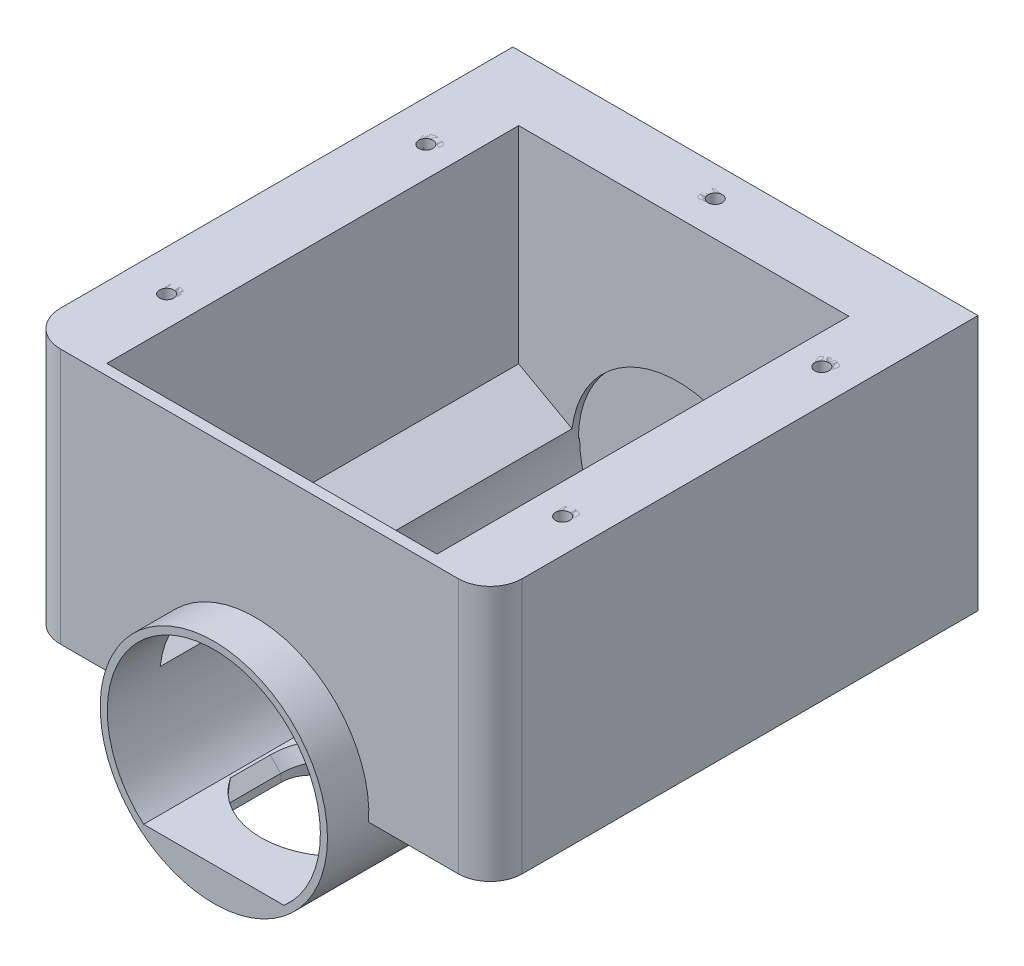
SolidWorks part; units mm, degrees
ref_plane "Front Plane" through (0, 0, 0) normal (0, 0, 1) x (1, 0, 0)
ref_plane "Top Plane" through (0, 0, 0) normal (0, 1, 0) x (1, 0, 0)
ref_plane "Right Plane" through (0, 0, 0) normal (1, 0, 0) x (0, 0, -1)
sketch "Sketch1" plane through (0, 0, 0) normal (0, 0, 1) x (1, 0, 0)
  circle A0 centre (0, 0) radius 30
  circle A1 centre (0, 0) radius 32
  dimension "D1" = 60
  dimension "D2" = 2
extrude "Boss-Extrude1" add sketch "Sketch1" along normal blind 60
sketch "Sketch3" plane through (0, 0, 0) normal (0, 0, -1) x (-1, 0, 0)
  line L0 (-32, 0) -> (-30, 0)
  line L2 (30, 0) -> (32, 0)
  arc A0 (-30, 0) -> (30, 0) centre (0, 0) ccw
  arc A1 (-32, 0) -> (32, 0) centre (0, 0) ccw
extrude "Boss-Extrude3" add sketch "Sketch3" along normal blind 120 contours A1 L2 A0 L0
sketch "Sketch4" plane through (0, 0, -120) normal (0, 0, -1) x (-1, 0, 0)
  circle A0 centre (0, 0) radius 32
extrude "Boss-Extrude4" add sketch "Sketch4" along normal blind 3 contours A0
sketch "Sketch5" plane through (0, 0, -123) normal (0, 0, -1) x (-1, 0, 0)
  line L5 (-1.05, 9.55) -> (1.05, 9.55)
  line L6 (-1.05, 9.55) -> (-1.05, 8.4349)
  line L12 (1.05, 9.55) -> (1.05, 8.4349)
  line L16 (-1.05, -8.4349) -> (-1.05, -9.55)
  line L17 (-1.05, -9.55) -> (1.05, -9.55)
  line L18 (1.05, -8.4349) -> (1.05, -9.55)
  arc A1 (1.05, -8.4349) -> (1.05, 8.4349) centre (0, 0) ccw
  arc A2 (-1.05, 8.4349) -> (-1.05, -8.4349) centre (0, 0) ccw
  point P3 (0, 8.5)
  point P8 (0, -8.5)
  dimension "D1" = 17
  dimension "D2" = 2.1
extrude "Cut-Extrude2" cut sketch "Sketch5" against normal blind 3
ref_plane "Plane1" through (0, 0, 0) normal (0, 1, 0) x (1, 0, 0)
sketch "Sketch6" plane through (0, 0, 0) normal (0, 1, 0) x (1, 0, 0)
  line L0 (32, 120) -> (30, 120) construction
  line L1 (-32, 0) -> (31.9951, 0)
  line L2 (-32, 0) -> (-32, 120)
  line L3 (-32, 120) -> (31.9951, 120)
  line L4 (31.9951, 0) -> (31.9951, 120)
  line L6 (-46.8095, 119.6619) -> (53.1905, 119.6619)
  line L7 (-46.8095, 119.6619) -> (-46.8095, -0.3381)
  line L8 (-46.8095, -0.3381) -> (53.1905, -0.3381)
  line L9 (53.1905, 119.6619) -> (53.1905, -0.3381)
  line L10 (-44.8095, 117.6619) -> (51.1905, 117.6619)
  line L11 (-44.8095, 117.6619) -> (-44.8095, 1.6619)
  line L12 (-44.8095, 1.6619) -> (51.1905, 1.6619)
  line L13 (51.1905, 117.6619) -> (51.1905, 1.6619)
  dimension "D1" = 100
  dimension "D2" = 2
  dimension "D3" = 2
  dimension "D4" = 2
  dimension "D5" = 2
extrude "Boss-Extrude11" add sketch "Sketch6" against normal blind 2 contours L10 L13 L12 L4 L1 L2 L11 L6 L7 L8 L9 | L2 L10 L4 L6 | L12 L2 L1 L4 region at (-0.0025, 0, -0.831) region at (-0.0025, 0, 0.1562) region at (-0.0025, 0, -118.6619)
extrude "Boss-Extrude12" add sketch "Sketch6<8>" along normal blind 70 contours L2 L10 L4 L6 | L10 L13 L12 L4 L1 L2 L11 L6 L7 L8 L9 | L12 L2 L1 L4 region at (-0.0025, 0, -0.831) region at (-0.0025, 0, 0.1562) region at (-0.0025, 0, -118.6619)
sketch "Sketch6<8>" plane through (0, 0, 0) normal (0, 1, 0) x (1, 0, 0) same geometry as "Sketch6"
ref_plane "Plane2" through (0, 0, -117.6619) normal (0, 0, 1) x (1, 0, 0)
sketch "Sketch8" plane through (0, 0, -119.6619) normal (0, 0, -1) x (-1, 0, 0)
  line L0 (46.8095, 13) -> (19.6795, -2)
  line L1 (-53.1905, -2) -> (-26.0645, -2)
  line L2 (-53.1905, -2) -> (-53.1905, 14)
  line L5 (46.8095, -2) -> (19.6795, -2)
  line L6 (46.8095, -2) -> (46.8095, 13)
  line L9 (-53.1905, 14) -> (-26.0645, -2)
  dimension "D1" = 16
  dimension "D2" = 27.13
  dimension "D4" = 15
extrude "Boss-Extrude14" add sketch "Sketch8" against normal blind 120
ref_plane "Plane3" through (0, 0, 60) normal (0, 0, 1) x (1, 0, 0)
sketch "Sketch10" plane through (0, 0, 60) normal (0, 0, 1) x (1, 0, 0)
  circle A0 centre (0, 0) radius 30
extrude "Cut-Extrude3" cut sketch "Sketch10" against normal blind 180 contours A0
ref_plane "Plane4" through (0, -2, 0) normal (0, -1, 0) x (-1, 0, 0)
sketch "Sketch11" plane through (0, -2, 0) normal (0, -1, 0) x (-1, 0, 0)
  line L0 (0, 123) -> (0, -60) construction
  line L1 (32, 123) -> (-32, 123) construction
  line L2 (-32, -60) -> (32, -60) construction
  circle A0 centre (0, 106.678) radius 2
  circle A1 centre (0, 74.9444) radius 2
  circle A2 centre (0, 18.4657) radius 2
  circle A3 centre (0, 43.5664) radius 2
  dimension "D1" = 31.7336
ref_plane "Plane5" through (0, 0, 60) normal (0, 0, 1) x (1, 0, 0)
sketch "Sketch12" plane through (0, 0, 60) normal (0, 0, 1) x (1, 0, 0)
  line L0 (0, -40) -> (0, 0.6822) construction
  circle A5 centre (0, 0) radius 32
  circle A6 centre (0, -26.2661) radius 13.6282
  circle A7 centre (0, -26.2661) radius 11.6282
  point P9 (0, -26.2661)
  dimension "D1" = 2
  dimension "D2" = 64
extrude "Boss-Extrude16" add sketch "Sketch12<4>" against normal blind 71 contours A7 L0 A5 | L0 A7 A5 region at (-4.4798, -34.0319, 60) region at (4.4798, -34.0319, 60)
sketch "Sketch12<4>" plane through (0, 0, 60) normal (0, 0, 1) x (1, 0, 0) same geometry as "Sketch12"
extrude "Cut-Extrude6" cut sketch "Sketch12<5>" against normal blind 69 contours L0 A7 A5 | A7 L0 A5 | L0 A6 A5 A7 | A6 L0 A7 A5 region at (-7.1656, -35.6219, 60) region at (7.1656, -35.6219, 60) region at (-4.4798, -34.0319, 60) region at (4.4798, -34.0319, 60)
sketch "Sketch12<5>" plane through (0, 0, 60) normal (0, 0, 1) x (1, 0, 0) same geometry as "Sketch12"
sketch "Sketch13" plane through (0, 0, -119.6619) normal (0, 0, -1) x (-1, 0, 0)
  line L0 (31.9374, -2) -> (46.8095, -2)
  line L1 (-53.1905, 70) -> (46.8095, 70)
  line L2 (-53.1905, 70) -> (-53.1905, -2)
  line L3 (-53.1905, -2) -> (-31.9374, -2)
  line L4 (46.8095, 70) -> (46.8095, -2)
  arc A0 (31.9374, -2) -> (-31.9374, -2) centre (0, 0) ccw
extrude "Boss-Extrude17" add sketch "Sketch13" along normal blind 3.35
ref_plane "Plane6" through (0, -45, 0) normal (0, -1, 0) x (-1, 0, 0)
ref_plane "Plane7" through (0, 0, -9) normal (0, 0, 1) x (1, 0, 0)
extrude "Cut-Extrude11" cut sketch "Sketch12" against normal blind 110 contours A7 L0 A5 | L0 A7 A5 | A6 L0 A7 A5 | L0 A6 A5 A7 region at (-7.1656, -35.6219, 60) region at (7.1656, -35.6219, 60) region at (-4.4798, -34.0319, 60) region at (4.4798, -34.0319, 60)
ref_plane "Plane8" through (-46.8095, 0, 0) normal (-1, 0, 0) x (0, 0, 1)
sketch "Sketch16" plane through (-46.8095, 0, 0) normal (-1, 0, 0) x (0, 0, 1)
  line L3 (23, -32) -> (60, -32)
  line L4 (60, 32) -> (60, -32)
  line L5 (60, 32) -> (23, 32)
  line L6 (60, 32) -> (0.3381, 32) construction
  line L7 (23, 32) -> (23, -32)
  dimension "D1" = 37
ref_plane "Plane10" through (0, -52, 0) normal (0, -1, 0) x (-1, 0, 0)
sketch "Sketch18" plane through (0, -52, 0) normal (0, -1, 0) x (-1, 0, 0)
  line L0 (0, 0) -> (0, 21.7329) construction
  line L1 (-15.8772, 6.8416) -> (-15.8772, 21.7329)
  line L2 (15.8772, 6.8416) -> (15.8772, 21.7329)
  arc A1 (15.8772, 21.7329) -> (-15.8772, 21.7329) centre (0, 21.7329) ccw
  arc A2 (15.8772, 6.8416) -> (-15.8772, 6.8416) centre (0, 22.7187) cw
  point P3 (0, 10.8665)
extrude "Cut-Extrude15" cut sketch "Sketch16" against normal blind 94
extrude "Cut-Extrude16" cut sketch "Sketch18" against normal blind 34
sketch "Sketch19" plane through (0, 70, 0) normal (0, 1, 0) x (1, 0, 0)
  line L0 (-46.8095, 123.0119) -> (53.1905, 123.0119) construction
  line L1 (-56.8095, 133.0119) -> (63.1905, 133.0119)
  line L2 (-56.8095, 133.0119) -> (-56.8095, 2.6619)
  line L3 (-56.8095, -0.3381) -> (-46.8095, -0.3381)
  line L4 (63.1905, 133.0119) -> (63.1905, 2.6619)
  line L5 (53.1905, 123.0119) -> (53.1905, -0.3381) construction
  line L6 (-46.8095, 123.0119) -> (-46.8095, -0.3381) construction
  line L7 (-46.8095, -0.3381) -> (53.1905, -0.3381) construction
  line L8 (-56.8095, 2.6619) -> (-46.8095, 2.6619)
  line L9 (-59.8095, 136.0119) -> (66.1905, 136.0119)
  line L10 (-59.8095, 136.0119) -> (-59.8095, -0.3381)
  line L11 (-59.8095, -0.3381) -> (-46.8095, -0.3381)
  line L12 (66.1905, 136.0119) -> (66.1905, -0.3381)
  line L13 (53.1905, -0.3381) -> (53.1905, 2.6619)
  line L14 (-46.8095, -0.3381) -> (-46.8095, 2.6619)
  line L15 (53.1905, 2.6619) -> (63.1905, 2.6619)
  line L16 (53.1905, -0.3381) -> (63.1905, -0.3381)
  line L17 (53.1905, -0.3381) -> (66.1905, -0.3381)
  line L19 (63.1905, 2.6619) -> (-56.8095, 2.6619)
  line L20 (63.1905, 2.6619) -> (63.1905, 133.0119)
  line L21 (63.1905, 133.0119) -> (-56.8095, 133.0119)
  line L22 (-56.8095, 2.6619) -> (-56.8095, 133.0119)
  line M12 (53.1905, -0.3381) -> (53.1905, 123.0119)
  line M13 (53.1905, 123.0119) -> (-46.8095, 123.0119)
  line M14 (-46.8095, 123.0119) -> (-46.8095, -0.3381)
  dimension "D1" = 10
  dimension "D2" = 10
  dimension "D3" = 10
  dimension "D4" = 3
  dimension "D5" = 3
  dimension "D6" = 3
  dimension "D7" = 3
extrude "Boss-Extrude20" add sketch "Sketch19" against normal blind 72 contours L16 L17 L12 L9 L10 L11 L3 L8 L2 L1 L4 L15 M14 M12 region at (-58.6661, 70, -67.8369)
extrude "Boss-Extrude21" add sketch "Sketch19<4>" against normal blind 3 contours L15 L4 L1 L2 L8 M12 M14 M13 region at (3.1905, 70, -131.2402)
sketch "Sketch19<4>" plane through (0, 70, 0) normal (0, 1, 0) x (1, 0, 0) same geometry as "Sketch19"
sketch "Sketch21" plane through (0, 0, -123) normal (0, 0, -1) x (-1, 0, 0)
  circle A0 centre (0, 0) radius 32
extrude "Cut-Extrude17" cut sketch "Sketch21" along normal blind 34
sketch "Sketch22" plane through (0, 0, -136.0119) normal (0, 0, -1) x (-1, 0, 0)
  line L0 (59.8095, 70) -> (-66.1905, 70) construction
  line L1 (-66.1905, 70) -> (-51.1905, 70)
  line L2 (-66.1905, 70) -> (-66.1905, 57)
  line L3 (-66.1905, 57) -> (-51.1905, 57)
  line L4 (-51.1905, 70) -> (-51.1905, 57)
  line L6 (44.3736, 70) -> (59.8095, 70)
  line L7 (44.3736, 70) -> (44.3736, 57)
  line L8 (44.3736, 57) -> (59.8095, 57)
  line L9 (59.8095, 70) -> (59.8095, 57)
  line L10 (59.8095, -2) -> (59.8095, 70) construction
  circle A0 centre (-58.6905, 63.5) radius 1.5
  circle A1 centre (52.0916, 63.5) radius 1.5
  dimension "D4" = 3
  dimension "D1" = 13
  dimension "D2" = 15
  dimension "D3" = 13
extrude "Boss-Extrude23" add sketch "Sketch22" against normal blind 10
extrude "Cut-Extrude19" cut sketch "Sketch22<2>" against normal blind 17 and the other way blind 20 contours A0 | A1
sketch "Sketch22<2>" plane through (0, 0, -136.0119) normal (0, 0, -1) x (-1, 0, 0) same geometry as "Sketch22"
sketch "Sketch23" plane through (0, 0, 23) normal (0, 0, 1) x (1, 0, 0)
  line L2 (-19.7809, -22.5547) -> (19.7809, -22.5547)
  arc A0 (-19.7809, -22.5547) -> (19.7809, -22.5547) centre (0, 0) ccw
extrude "Boss-Extrude24" add sketch "Sketch23" against normal blind 145
ref_plane "Plane11" through (19.7809, -22.5547, 23) normal (0, 0, 1) x (1, 0, 0)
ref_plane "Plane12" through (0, 0, -37.6101) normal (0, 0, 1) x (1, 0, 0)
sketch "Sketch25" plane through (0, 0, -37.6101) normal (0, 0, 1) x (1, 0, 0)
  circle A0 centre (19.7809, -22.5547) radius 1.2
  circle A1 centre (-19.7809, -22.5547) radius 1.2
extrude "Cut-Extrude21" cut sketch "Sketch25" against normal blind 82
ref_plane "Plane15" through (0, -22.5547, 0) normal (0, 1, 0) x (1, 0, 0)
extrude "Cut-Extrude22" cut sketch "Sketch18<3>" against normal blind 36
sketch "Sketch18<3>" plane through (0, -52, 0) normal (0, -1, 0) x (-1, 0, 0) same geometry as "Sketch18"
ref_plane "Plane17" through (0, 0, 0.3381) normal (0, 0, 1) x (1, 0, 0)
sketch "Sketch29" plane through (0, 0, 0.3381) normal (0, 0, 1) x (1, 0, 0)
  line L0 (-59.8095, -2) -> (-31.9374, -2) construction
  line L1 (31.9374, -2) -> (66.1905, -2) construction
  line L2 (66.1905, -2) -> (66.1905, 70) construction
  line L3 (-59.8095, 70) -> (66.1905, 70) construction
  line L4 (-59.8095, -2) -> (-59.8095, 70) construction
  line L5 (-59.8095, -2) -> (-31.9374, -2)
  line L6 (31.9374, -2) -> (66.1905, -2)
  line L7 (66.1905, -2) -> (66.1905, 70)
  line L8 (-59.8095, 70) -> (66.1905, 70)
  line L9 (-59.8095, -2) -> (-59.8095, 70)
  arc A0 (31.9374, -2) -> (-31.9374, -2) centre (0, 0) ccw construction
  arc A1 (31.9374, -2) -> (-31.9374, -2) centre (0, 0) ccw
extrude "Boss-Extrude34" add sketch "Sketch29" along normal blind 1
sketch "Sketch30" plane through (-59.8095, 0, 0) normal (-1, 0, 0) x (0, 0, 1)
  line L1 (-136.0119, 70) -> (1.3381, 70)
  line L2 (-136.0119, 70) -> (-136.0119, -2)
  line L3 (-136.0119, -2) -> (1.3381, -2)
  line L4 (1.3381, 70) -> (1.3381, -2)
extrude "Boss-Extrude35" add sketch "Sketch30" along normal blind 5
sketch "Sketch32" plane through (51.1905, 0, 0) normal (-1, 0, 0) x (0, 0, 1)
  line L0 (-117.6619, 12.8203) -> (-117.6619, 9.9819)
  line L1 (-117.6619, 3.5871) -> (-117.6619, 11.8942) construction
  line L2 (-117.6619, 9.9819) -> (-1.6619, 9.9819)
  line L3 (-1.6619, 3.5871) -> (-1.6619, 11.8942) construction
  line L4 (-117.6619, 12.8203) -> (-1.6619, 12.8203)
  line L5 (-1.6619, 12.8203) -> (-1.6619, 70)
  line L6 (-1.6619, 70) -> (-117.6619, 70)
  line L7 (-117.6619, 70) -> (-117.6619, 12.8203)
  line L9 (-1.6619, 12.8203) -> (-1.6619, 70)
  line L10 (-1.6619, 70) -> (-117.6619, 70)
  line L11 (-117.6619, 70) -> (-117.6619, 12.8203)
  line L12 (-1.6619, 9.9819) -> (-1.6619, 12.8203)
  dimension "D1" = 0
extrude "Boss-Extrude38" add sketch "Sketch32" along normal blind 3
sketch "Sketch34" plane through (0, -2, 0) normal (0, -1, 0) x (1, 0, 0)
  circle A0 centre (-40.0595, -95.4633) radius 1.5
  circle A1 centre (-40.0595, -29.4633) radius 1.5
  circle A2 centre (41.4405, -29.4633) radius 1.5
  circle A3 centre (41.4405, -95.4633) radius 1.5
extrude "Cut-Extrude24" cut sketch "Sketch34" against normal blind 5
sketch "Sketch35" plane through (0, 0, -123) normal (0, 0, -1) x (-1, 0, 0)
  line L0 (-31.9374, -2) -> (-29.9333, -2)
  line L1 (29.9333, -2) -> (31.9374, -2)
  circle A0 centre (0, 0) radius 30
  arc A2 (-31.9374, -2) -> (31.9374, -2) centre (0, 0) ccw
  arc A3 (31.9374, -2) -> (-31.9374, -2) centre (0, 0) ccw
  arc A4 (-31.9374, -2) -> (31.9374, -2) centre (0, 0) ccw
  arc A5 (31.9374, -2) -> (-31.9374, -2) centre (0, 0) ccw
  arc M11 (-31.9374, -2) -> (31.9374, -2) centre (0, 0) ccw
  arc M12 (31.9374, -2) -> (-31.9374, -2) centre (0, 0) ccw
  dimension "D2" = 2
  dimension "D1" = 0
extrude "Boss-Extrude45" add sketch "Sketch35" along normal blind 9 contours A0 L0 L1 M11 | A0 L1 L0 M12 region at (0, 31.2753, -123) region at (30.9353, -2.7057, -123)
sketch "Sketch36" plane through (0, 0, -132) normal (0, 0, -1) x (-1, 0, 0)
  line L0 (31.2056, -7.0858) -> (29.1512, -7.0858)
  line L1 (-29.1512, -7.0858) -> (-31.2056, -7.0858)
  arc A0 (29.1512, -7.0858) -> (-29.1512, -7.0858) centre (0, 0) ccw
  circle A1 centre (0, 0) radius 32
  arc A2 (31.2056, -7.0858) -> (-31.2056, -7.0858) centre (0, 0) ccw
  dimension "D1" = 0
extrude "Cut-Extrude30" cut sketch "Sketch36" against normal blind 9
sketch "Sketch37" plane through (0, 0, 23) normal (0, 0, 1) x (1, 0, 0)
  circle A1 centre (0, 0) radius 32
  circle A2 centre (0, 0) radius 32
  dimension "D1" = 0
extrude "Cut-Extrude31" cut sketch "Sketch37" against normal blind 10
sketch "Sketch38" plane through (0, 70, 0) normal (0, 1, 0) x (1, 0, 0)
  line L2 (48.1905, 1.6619) -> (48.1905, 117.6619) construction
  line L3 (-64.8095, 136.0119) -> (66.1905, 136.0119) construction
  circle A0 centre (0.6905, 127.5119) radius 2
  circle A1 centre (56.6905, 101.5251) radius 2
  circle A2 centre (56.6905, 28.5251) radius 2
  circle A3 centre (-53.3127, 100.0119) radius 2
  circle A4 centre (-53.3127, 27.0119) radius 2
  circle A5 centre (0.6905, 127.5119) radius 3.5
  circle A6 centre (56.6905, 101.5251) radius 3.5
  circle A7 centre (56.6905, 28.5251) radius 3.5
  circle A8 centre (-53.3127, 100.0119) radius 3.5
  circle A9 centre (-53.3127, 27.0119) radius 3.5
  dimension "D1" = 4
  dimension "D2" = 73
  dimension "D8" = 4
  dimension "D9" = 7
  dimension "D10" = 7
  dimension "D11" = 4
  dimension "D12" = 7
  dimension "D13" = 7
  dimension "D14" = 4
  dimension "D15" = 7
  dimension "D16" = 4
  dimension "D3" = 73
  dimension "D4" = 8.5
  dimension "D5" = 110.0032
  dimension "D6" = 36
  dimension "D7" = 8.5
extrude "Boss-Extrude64" add sketch "Sketch38" against normal blind 11 separate body contours A6 | A5 | A7 | A9 | A8
extrude "Cut-Extrude33" cut sketch "Sketch38<8>" against normal blind 9 contours A2 | A4 | A1 | A3 | A0
sketch "Sketch38<8>" plane through (0, 70, 0) normal (0, 1, 0) x (1, 0, 0) same geometry as "Sketch38"
chamfer "Chamfer1" distance 3 angle 45 3 edges at (15.8772, -22.5547, -14.2872) (-15.8772, -22.5547, -14.2872) (0, -22.5547, -37.6101)
fillet "Fillet1" radius 10 1 edges at (-64.8095, 34, 1.3381)
fillet "Fillet2" radius 9 1 edges at (66.1905, 34, 1.3381)
